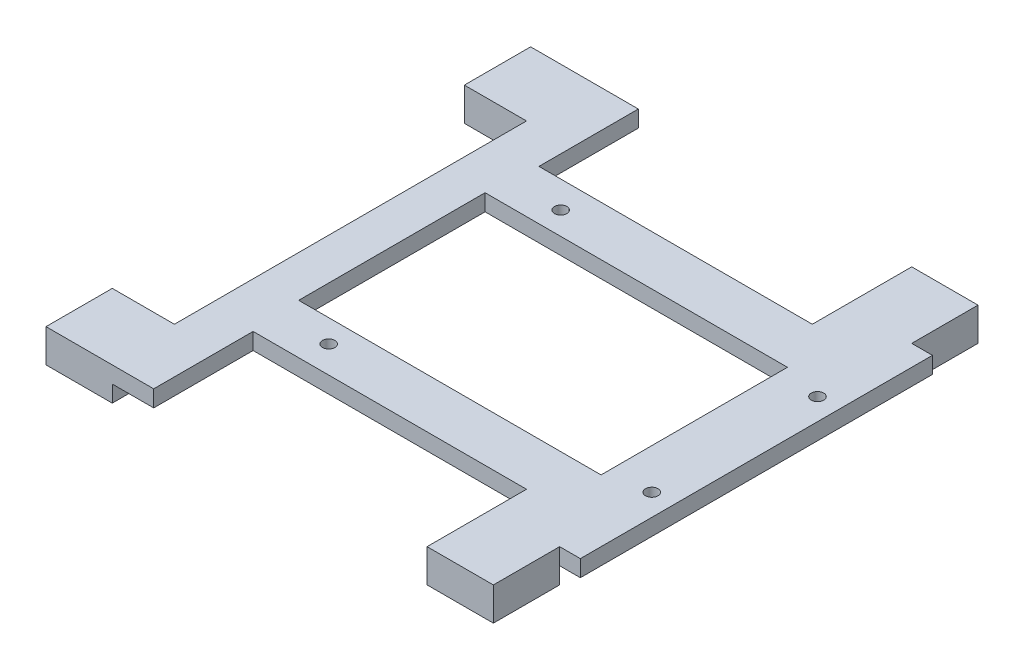
SolidWorks part; units mm, degrees
ref_plane "Front Plane" through (0, 0, 0) normal (0, 0, 1) x (1, 0, 0)
ref_plane "Top Plane" through (0, 0, 0) normal (0, 1, 0) x (1, 0, 0)
ref_plane "Right Plane" through (0, 0, 0) normal (1, 0, 0) x (0, 0, -1)
sketch "Sketch1" plane through (0, 0, 0) normal (0, 1, 0) x (1, 0, 0)
  line L1 (-56.5, 42.5) -> (56.5, 42.5)
  line L2 (-56.5, 42.5) -> (-56.5, -42.5)
  line L3 (-56.5, -42.5) -> (56.5, -42.5)
  line L4 (56.5, 42.5) -> (56.5, -42.5)
  line L5 (-56.5, 42.5) -> (56.5, -42.5) construction
  line L6 (-56.5, -42.5) -> (56.5, 42.5) construction
  point P0 (0, 0)
  dimension "D1" = 113
  dimension "D2" = 85
extrude "Boss-Extrude1" add sketch "Sketch1" along normal blind 4
sketch "Sketch2" plane through (0, 4, 0) normal (0, 1, 0) x (1, 0, 0)
  line L0 (0, 42.5) -> (0, -42.5) construction
  line L1 (56.5, 42.5) -> (-56.5, 42.5) construction
  line L2 (-56.5, -42.5) -> (56.5, -42.5) construction
  line L4 (-56.5, 0) -> (56.5, 0) construction
  line L5 (-56.5, 42.5) -> (-56.5, -42.5) construction
  line L6 (56.5, -42.5) -> (56.5, 42.5) construction
  circle A46 centre (-18.75, 28) radius 1.5
  circle A47 centre (-18.75, -28) radius 1.5
  circle A48 centre (51.25, -20) radius 1.5
  circle A49 centre (51.25, 20) radius 1.5
  point P20 (22.5, 0)
  line B0 (-25.4814, 0) -> (70.4814, 0) construction
  arc B1 (-19.5394, -30.8943) -> (-19.2077, -30.9649) centre (-18.75, -28) ccw construction
  arc B2 (-21.6443, -28.7894) -> (-19.5394, -30.8943) centre (-18.75, -28) ccw construction
  arc B3 (-21.7149, -28.4577) -> (-21.6443, -28.7894) centre (-18.75, -28) ccw construction
  arc B4 (-19.2077, 30.9649) -> (-19.5394, 30.8943) centre (-18.75, 28) ccw construction
  arc B5 (-19.5394, 30.8943) -> (-21.6443, 28.7894) centre (-18.75, 28) ccw construction
  arc B6 (-21.6443, 28.7894) -> (-21.7149, 28.4577) centre (-18.75, 28) ccw construction
  arc B7 (-21.7149, 28.4577) -> (-21.7149, -28.4577) centre (83.9083, 0) ccw construction
  arc B8 (-19.2077, -30.9649) -> (9.25, -34.7314) centre (9.25, 74.6583) ccw construction
  arc B9 (9.25, -34.7314) -> (63.3655, -15.1715) centre (9.25, 49.9083) ccw construction
  arc B10 (63.3655, -15.1715) -> (63.3655, 15.1715) centre (50.75, 0) ccw construction
  arc B11 (63.3655, 15.1715) -> (9.25, 34.7314) centre (9.25, -49.9083) ccw construction
  arc B12 (9.25, 34.7314) -> (-19.2077, 30.9649) centre (9.25, -74.6583) ccw construction
  arc B13 (51.25, 22.5132) -> (51.25, 17.4868) centre (51.25, 20) ccw construction
  arc B14 (51.25, 17.5) -> (51.25, 22.5) centre (51.25, 20) ccw construction
  arc B15 (51.25, -17.5) -> (51.25, -22.5) centre (51.25, -20) ccw construction
  arc B16 (51.25, -22.5132) -> (51.25, -17.4868) centre (51.25, -20) ccw construction
  arc B17 (-18.75, -25.5) -> (-18.75, -30.5) centre (-18.75, -28) ccw construction
  arc B18 (-18.75, -30.5132) -> (-18.75, -25.4868) centre (-18.75, -28) ccw construction
  arc B19 (-18.75, 30.5) -> (-18.75, 25.5) centre (-18.75, 28) ccw construction
  arc B20 (-18.75, 25.5) -> (-18.75, 30.5) centre (-18.75, 28) ccw construction
  dimension "D1" = 3
  dimension "D2" = 3
  dimension "D3" = 3
  dimension "D4" = 3
  dimension "D5" = 34
sketch_block_instance "Block2-1"
sketch_block "Block2"
extrude "Cut-Extrude1" cut sketch "Sketch2" against normal through all contours A46 | A49 | A47 | A48
sketch "Sketch4" plane through (0, 0, 0) normal (0, -1, 0) x (1, 0, 0)
  line L0 (-56.5, 42.5) -> (56.5, 42.5) construction
  line L5 (-56.5, 42.5) -> (-40.5, 42.5)
  line L6 (-56.5, 42.5) -> (-56.5, 58.5)
  line L7 (-56.5, 58.5) -> (-40.5, 58.5)
  line L8 (-40.5, 42.5) -> (-40.5, 58.5)
  line L9 (51.5, 42.5) -> (35.5, 42.5)
  line L10 (51.5, 42.5) -> (51.5, 58.5)
  line L11 (51.5, 58.5) -> (35.5, 58.5)
  line L12 (35.5, 42.5) -> (35.5, 58.5)
  line L18 (56.5, 42.5) -> (56.5, -42.5) construction
  line L19 (0, 0) -> (-56.5, 0) construction
  line L20 (-56.5, -42.5) -> (-56.5, 42.5) construction
  line L21 (51.5, -58.5) -> (35.5, -58.5)
  line L22 (35.5, -42.5) -> (35.5, -58.5)
  line L23 (51.5, -42.5) -> (35.5, -42.5)
  line L24 (51.5, -42.5) -> (51.5, -58.5)
  line L25 (-56.5, -58.5) -> (-40.5, -58.5)
  line L26 (-40.5, -42.5) -> (-40.5, -58.5)
  line L27 (-56.5, -42.5) -> (-40.5, -42.5)
  line L28 (-56.5, -42.5) -> (-56.5, -58.5)
  dimension "D1" = 16
  dimension "D2" = 16
  dimension "D3" = 5
  dimension "D4" = 16
  dimension "D5" = 16
extrude "Boss-Extrude3" add sketch "Sketch4" against normal up to surface (4 mm away) and the other way blind 1 up to face at (-18.75, 4, -26.5)
sketch "Sketch10" plane through (0, 4, 0) normal (0, 1, 0) x (1, 0, 0)
  line L0 (-40.5, -58.5) -> (-56.5, -58.5) construction
  line L1 (-40.5, -42.5) -> (-30.5, -42.5)
  line L2 (-40.5, -42.5) -> (-40.5, -58.5)
  line L3 (-40.5, -58.5) -> (-30.5, -58.5)
  line L4 (-30.5, -42.5) -> (-30.5, -58.5)
  line L5 (-40.5, 42.5) -> (-30.5, 42.5)
  line L6 (-40.5, 42.5) -> (-40.5, 58.5)
  line L7 (-40.5, 58.5) -> (-30.5, 58.5)
  line L8 (-30.5, 42.5) -> (-30.5, 58.5)
  line L9 (-56.5, 58.5) -> (-40.5, 58.5) construction
  dimension "D1" = 10
  dimension "D2" = 10
extrude "Boss-Extrude6" add sketch "Sketch10" against normal up to surface (4 mm away) up to face at (-18.75, 0, -26.5)
sketch "Sketch6" plane through (0, 4, 0) normal (0, 1, 0) x (1, 0, 0)
  line L0 (35.5, 42.5) -> (35.5, 58.5) construction
  line L1 (-31.5, 22.5) -> (41.5, 22.5)
  line L2 (-31.5, 22.5) -> (-31.5, -22.5)
  line L3 (-31.5, -22.5) -> (41.5, -22.5)
  line L4 (41.5, 22.5) -> (41.5, -22.5)
  line L5 (35.5, -58.5) -> (35.5, -42.5) construction
  line L6 (35.5, 42.5) -> (-30.5, 42.5) construction
  line L7 (-30.5, -42.5) -> (35.5, -42.5) construction
  line L8 (-56.5, 58.5) -> (-56.5, -58.5) construction
  line L9 (-41.5, 0) -> (-56.5, 0) construction
  line L10 (-56.5, 42.5) -> (-41.5, 42.5)
  line L11 (-56.5, 42.5) -> (-56.5, -42.5)
  line L12 (-56.5, -42.5) -> (-41.5, -42.5)
  line L13 (-41.5, 42.5) -> (-41.5, -42.5)
  line L14 (-31.5, 0) -> (41.5, 0) construction
  line L15 (-30.5, 42.5) -> (35.5, 42.5)
  line L16 (-30.5, 42.5) -> (-30.5, 34.5)
  line L17 (-30.5, 34.5) -> (35.5, 34.5)
  line L18 (35.5, 42.5) -> (35.5, 34.5)
  line L19 (-30.5, -42.5) -> (35.5, -42.5)
  line L20 (-30.5, -42.5) -> (-30.5, -34.5)
  line L21 (-30.5, -34.5) -> (35.5, -34.5)
  line L22 (35.5, -42.5) -> (35.5, -34.5)
  line L23 (56.5, -42.5) -> (56.5, 42.5) construction
  dimension "D1" = 20
  dimension "D2" = 20
  dimension "D3" = 25
  dimension "D4" = 15
  dimension "D5" = 85
  dimension "D6" = 8
  dimension "D7" = 8
  dimension "D8" = 15
extrude "Cut-Extrude2" cut sketch "Sketch6" against normal through all
sketch "Sketch8" plane through (0, -1, 0) normal (0, -1, 0) x (1, 0, 0)
  line L0 (-56.5, 58.5) -> (-40.5, 58.5) construction
  line L1 (-56.5, 58.5) -> (-56.5, 42.5) construction
  line L2 (-56.5, 42.5) -> (-40.5, 42.5) construction
  line L3 (-40.5, 58.5) -> (-40.5, 42.5) construction
  line L4 (35.5, 58.5) -> (51.5, 58.5) construction
  line L5 (35.5, 58.5) -> (35.5, 42.5) construction
  line L6 (35.5, 42.5) -> (51.5, 42.5) construction
  line L7 (51.5, 58.5) -> (51.5, 42.5) construction
  line L8 (-56.5, 58.5) -> (-40.5, 42.5) construction
  line L9 (-56.5, 42.5) -> (-40.5, 58.5) construction
  line L10 (35.5, 58.5) -> (51.5, 42.5) construction
  line L11 (35.5, 42.5) -> (51.5, 58.5) construction
  line L12 (51.5, 58.5) -> (35.5, 58.5) construction
  line L13 (0, 0) -> (-56.5, 0) construction
  line L14 (-56.5, 42.5) -> (-40.5, 42.5) construction
  line L15 (35.5, 42.5) -> (51.5, 42.5) construction
  circle A0 centre (-48.5, 50.5) radius 6.1
  circle A1 centre (43.5, 50.5) radius 6.1
  circle A2 centre (43.5, -50.5) radius 6.1
  circle A3 centre (-48.5, -50.5) radius 6.1
  dimension "D3" = 12.2
  dimension "D4" = 12.2
extrude "Cut-Extrude3" cut sketch "Sketch8" against normal blind 3.2
sketch "Sketch9" plane through (0, -1, 0) normal (0, -1, 0) x (1, 0, 0)
  line L0 (-55.5, 57.5) -> (-55.5, 43.5)
  line L1 (-56.5, 58.5) -> (-40.5, 58.5)
  line L2 (-56.5, 58.5) -> (-56.5, 42.5)
  line L3 (-56.5, 42.5) -> (-40.5, 42.5)
  line L4 (-40.5, 58.5) -> (-40.5, 42.5)
  line L5 (35.5, 58.5) -> (51.5, 58.5)
  line L6 (35.5, 58.5) -> (35.5, 42.5)
  line L7 (35.5, 42.5) -> (51.5, 42.5)
  line L8 (51.5, 58.5) -> (51.5, 42.5)
  line L9 (-55.5, 43.5) -> (-41.5, 43.5)
  line L10 (-41.5, 57.5) -> (-41.5, 43.5)
  line L11 (-55.5, 57.5) -> (-41.5, 57.5)
  line L16 (0, 0) -> (-56.5, 0) construction
  line L17 (36.5, -43.5) -> (50.5, -43.5)
  line L18 (36.5, -57.5) -> (36.5, -43.5)
  line L19 (50.5, -57.5) -> (36.5, -57.5)
  line L20 (50.5, 43.5) -> (50.5, 57.5)
  line L21 (50.5, 57.5) -> (36.5, 57.5)
  line L22 (36.5, 57.5) -> (36.5, 43.5)
  line L23 (36.5, 43.5) -> (50.5, 43.5)
  line L24 (50.5, 43.5) -> (50.5, 57.5)
  line L25 (50.5, 57.5) -> (36.5, 57.5)
  line L26 (36.5, 57.5) -> (36.5, 43.5)
  line L27 (36.5, 43.5) -> (50.5, 43.5)
  line L28 (50.5, -43.5) -> (50.5, -57.5)
  line L29 (-55.5, -57.5) -> (-41.5, -57.5)
  line L30 (-41.5, -57.5) -> (-41.5, -43.5)
  line L31 (-55.5, -43.5) -> (-41.5, -43.5)
  line L32 (51.5, -58.5) -> (51.5, -42.5)
  line L33 (35.5, -42.5) -> (51.5, -42.5)
  line L34 (35.5, -58.5) -> (35.5, -42.5)
  line L35 (35.5, -58.5) -> (51.5, -58.5)
  line L36 (-40.5, -58.5) -> (-40.5, -42.5)
  line L37 (-56.5, -42.5) -> (-40.5, -42.5)
  line L38 (-56.5, -58.5) -> (-56.5, -42.5)
  line L39 (-56.5, -58.5) -> (-40.5, -58.5)
  line L40 (-55.5, -57.5) -> (-55.5, -43.5)
  dimension "D1" = 1
  dimension "D2" = 1
extrude "Boss-Extrude5" add sketch "Sketch9" along normal blind 3
fillet "Fillet1" radius 0.2 4 edges at (43.5, -1, -44.4) (-48.5, -1, -44.4) (43.5, -1, 44.4) (-48.5, -1, 44.4)
